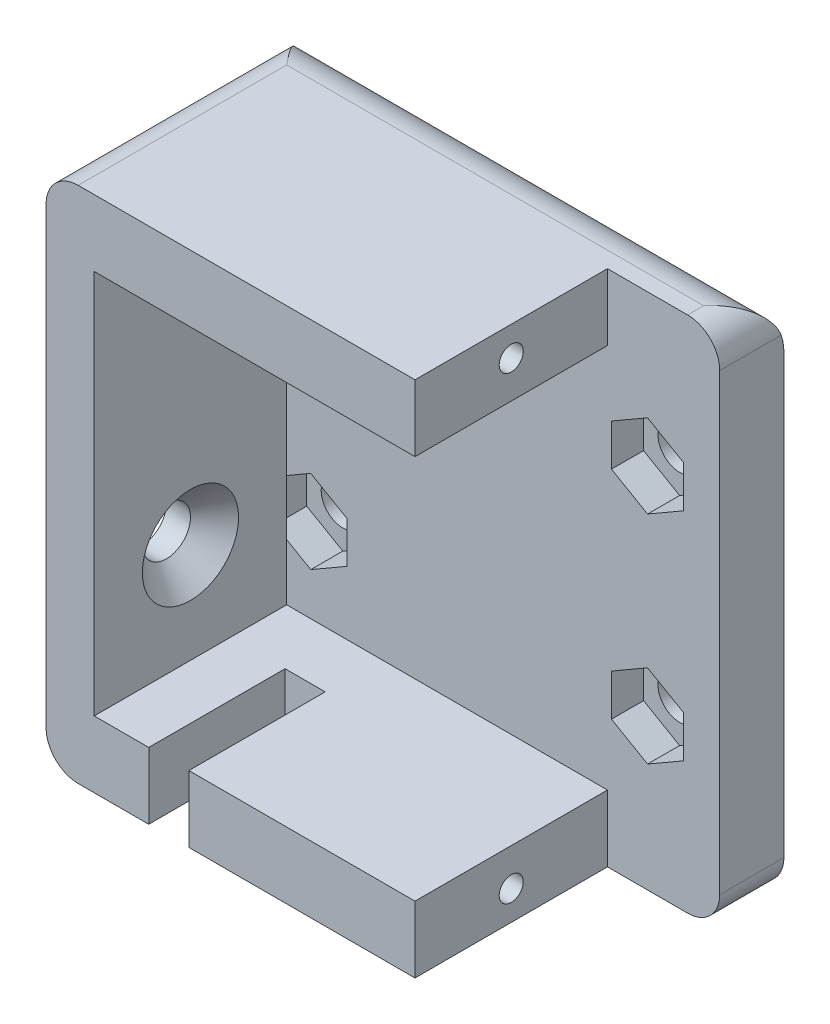
SolidWorks part; units mm, degrees
ref_plane "Спереди" through (0, 0, 0) normal (0, 0, 1) x (1, 0, 0)
ref_plane "Сверху" through (0, 0, 0) normal (0, 1, 0) x (1, 0, 0)
ref_plane "Справа" through (0, 0, 0) normal (1, 0, 0) x (0, 0, -1)
sketch "Эскиз1" plane through (0, 0, 0) normal (0, 0, 1) x (1, 0, 0)
  line L1 (-15, -16.15) -> (15, -16.15)
  line L2 (-15, -16.15) -> (-15, 16.15)
  line L3 (-15, 16.15) -> (15, 16.15)
  line L4 (15, -16.15) -> (15, 16.15)
  line L5 (-15, -16.15) -> (15, 16.15) construction
  line L6 (-15, 16.15) -> (15, -16.15) construction
  point P0 (0, 0)
  dimension "D1" = 30
  dimension "D2" = 32.3
extrude "тело" add sketch "Эскиз1" along normal blind 4
sketch "Эскиз2" plane through (0, 0, 4) normal (0, 0, 1) x (1, 0, 0)
  line L0 (8, 16.15) -> (-15, 16.15)
  line L1 (15, 16.15) -> (-15, 16.15) construction
  line L2 (-15, 16.15) -> (-15, -16.15)
  line L3 (-15, -16.15) -> (8, -16.15)
  line L4 (-15, -16.15) -> (15, -16.15) construction
  line L5 (8, -16.15) -> (8, -12)
  line L6 (8, -12) -> (-12, -12)
  line L8 (-12, 12) -> (8, 12)
  line L9 (8, 12) -> (8, 16.15)
  line L12 (-12, 12) -> (-12, -12)
  dimension "D1" = 20
  dimension "D3" = 24
  dimension "D4" = 3
extrude "крепление сервы" add sketch "Эскиз2" along normal blind 12
sketch "Эскиз4" plane through (-12, 0, 0) normal (1, 0, 0) x (0, 0, -1)
  line L0 (-10, 12) -> (-10, -12) construction
  line L1 (-16, 12) -> (-4, 12) construction
  line L2 (-16, -12) -> (-4, -12) construction
  circle A0 centre (-10, -5.77) radius 1.5
  dimension "D1" = 3
  dimension "D2" = 5.77
extrude "отверстие под выход второй оси" cut sketch "Эскиз4" against normal through all
chamfer "Фаска1" distance 1.5 angle 45 1 edges at (-12, -4.27, 10)
sketch "Эскиз3" plane through (8, 0, 0) normal (1, 0, 0) x (0, 0, -1)
  line L0 (-10, 16.15) -> (-10, 12) construction
  line L1 (-16, 16.15) -> (-4, 16.15) construction
  line L2 (-16, 12) -> (-4, 12) construction
  circle A0 centre (-10, 14.32) radius 0.75
  point P17 (-9, -5.77)
  dimension "D1" = 1.5
  dimension "D2" = 2.32
extrude "отверстие под саморез" cut sketch "Эскиз3" against normal blind 10
mirror "Зеркальное отражение2" about plane through (0, 0, 0) normal (0, 1, 0) of "отверстие под саморез"
sketch "Эскиз5" plane through (0, -16.15, 0) normal (0, -1, 0) x (1, 0, 0)
  line L0 (-15, 16) -> (8, 16) construction
  line L1 (-8.6, 16) -> (-6.1, 16)
  line L2 (-8.6, 16) -> (-8.6, 7.5)
  line L3 (-8.6, 7.5) -> (-6.1, 7.5)
  line L4 (-6.1, 16) -> (-6.1, 7.5)
  dimension "D1" = 2.5
  dimension "D2" = 3.4
  dimension "D3" = 8.5
extrude "паз для проводов" cut sketch "Эскиз5" against normal up to surface (4.15 mm away) up to face at (-2, -12, 10)
sketch "Эскиз6" plane through (0, 0, 0) normal (0, 0, -1) x (-1, 0, 0)
  line L0 (0, 16.15) -> (0, -16.15) construction
  line L1 (-15, 16.15) -> (15, 16.15) construction
  line L2 (15, -16.15) -> (-15, -16.15) construction
  line L4 (-14.25, -14.25) -> (14.25, -14.25) construction
  line L5 (-14.25, -14.25) -> (-14.25, 14.25) construction
  line L6 (-14.25, 14.25) -> (14.25, 14.25) construction
  line L7 (14.25, -14.25) -> (14.25, 14.25) construction
  line L8 (-14.25, -14.25) -> (14.25, 14.25) construction
  line L9 (-14.25, 14.25) -> (14.25, -14.25) construction
  circle A0 centre (-14.25, 14.25) radius 1.1
  circle A1 centre (14.25, 14.25) radius 1.1
  circle A2 centre (14.25, -14.25) radius 1.1
  circle A3 centre (-14.25, -14.25) radius 1.1
  point P6 (0, 0)
  dimension "D1" = 2.2
  dimension "D3" = 28.5
extrude "крепление камеры (большой)" [suppressed] cut sketch "Эскиз6" against normal through all
chamfer "Фаска2" [suppressed] distance 1 angle 45
fillet "Скругление1" radius 2 4 edges at (15, 16.15, 2) (15, -16.15, 2) (-15, -16.15, 8) (-15, 16.15, 8)
sketch "Эскиз7" plane through (0, 0, 0) normal (0, 0, -1) x (-1, 0, 0)
  line L1 (-10.5, 6.75) -> (10.5, 6.75) construction
  line L2 (-10.5, 6.75) -> (-10.5, -6.75) construction
  line L3 (-10.5, -6.75) -> (10.5, -6.75) construction
  line L4 (10.5, 6.75) -> (10.5, -6.75) construction
  line L5 (-10.5, 6.75) -> (10.5, -6.75) construction
  line L6 (-10.5, -6.75) -> (10.5, 6.75) construction
  circle A0 centre (10.5, 6.75) radius 1.35
  circle A1 centre (-10.5, 6.75) radius 1.35
  circle A2 centre (-10.5, -6.75) radius 1.35
  circle A3 centre (10.5, -6.75) radius 1.35
  point P0 (0, 0)
  dimension "D3" = 2.7
  dimension "D1" = 21
  dimension "D2" = 13.5
extrude "Отверстия под крепеж с верхней частью корпуса" cut sketch "Эскиз7" against normal up to next
sketch "Эскиз8" plane through (0, 0, 4) normal (0, 0, 1) x (1, 0, 0)
  line L0 (0, 16.15) -> (0, -16.15) construction
  line L1 (10.5, 9.3481) -> (8.25, 8.049)
  line L2 (8.25, 8.049) -> (8.25, 5.451)
  line L3 (8.25, 5.451) -> (10.5, 4.1519)
  line L4 (10.5, 4.1519) -> (12.75, 5.451)
  line L5 (12.75, 5.451) -> (12.75, 8.049)
  line L6 (12.75, 8.049) -> (10.5, 9.3481)
  line L7 (-15, 0) -> (15, 0) construction
  line L8 (15, -16.15) -> (15, 16.15) construction
  line L9 (-15, -16.15) -> (-15, 16.15) construction
  line L10 (-15, 16.15) -> (15, 16.15) construction
  line L11 (-15, -16.15) -> (15, -16.15) construction
  line L12 (-12.75, 8.049) -> (-10.5, 9.3481)
  line L13 (-12.75, 5.451) -> (-12.75, 8.049)
  line L14 (-10.5, 4.1519) -> (-12.75, 5.451)
  line L15 (-8.25, 5.451) -> (-10.5, 4.1519)
  line L16 (-8.25, 8.049) -> (-8.25, 5.451)
  line L17 (-10.5, 9.3481) -> (-8.25, 8.049)
  line L18 (-10.5, -9.3481) -> (-8.25, -8.049)
  line L19 (-8.25, -8.049) -> (-8.25, -5.451)
  line L20 (-8.25, -5.451) -> (-10.5, -4.1519)
  line L21 (-10.5, -4.1519) -> (-12.75, -5.451)
  line L22 (-12.75, -5.451) -> (-12.75, -8.049)
  line L23 (-12.75, -8.049) -> (-10.5, -9.3481)
  line L24 (12.75, -8.049) -> (10.5, -9.3481)
  line L25 (12.75, -5.451) -> (12.75, -8.049)
  line L26 (10.5, -4.1519) -> (12.75, -5.451)
  line L27 (8.25, -5.451) -> (10.5, -4.1519)
  line L28 (8.25, -8.049) -> (8.25, -5.451)
  line L29 (10.5, -9.3481) -> (8.25, -8.049)
  circle A1 centre (10.5, 6.75) radius 2.25 construction
  circle A2 centre (-10.5, 6.75) radius 2.25 construction
  circle A3 centre (-10.5, -6.75) radius 2.25 construction
  circle A4 centre (10.5, -6.75) radius 2.25 construction
  dimension "D1" = 4.5
extrude "Углубления под гайки" cut sketch "Эскиз8" against normal blind 2 contours L12 L17 L16 L15 L14 L13 | L1 L2 L3 L4 L5 L6 | L24 L29 L28 L27 L26 L25 | L18 L19 L20 L21 L22 L23
fillet "Скругление2" radius 3 1 edges at (0, 16.15, 0) tangent propagation no
